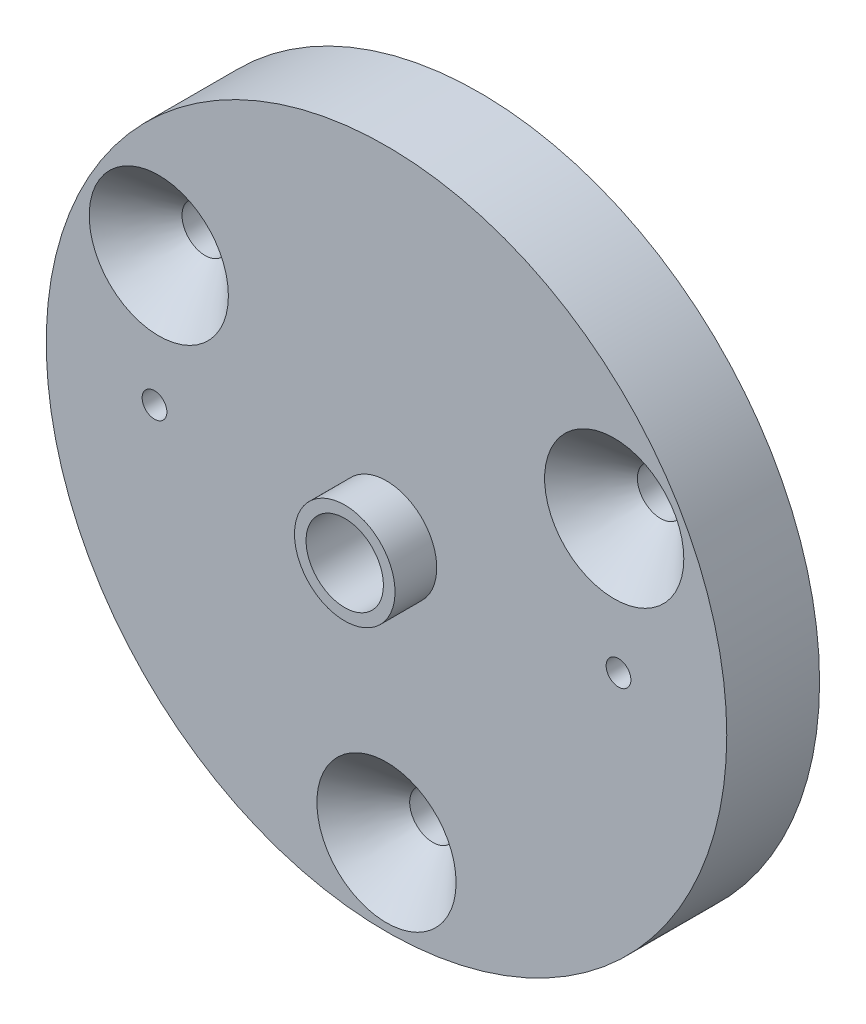
SolidWorks part; units mm, degrees
ref_plane "Спереди" through (0, 0, 0) normal (0, 0, 1) x (1, 0, 0)
ref_plane "Сверху" through (0, 0, 0) normal (0, 1, 0) x (1, 0, 0)
ref_plane "Справа" through (0, 0, 0) normal (1, 0, 0) x (0, 0, -1)
sketch "Эскиз1" plane through (0, 0, 0) normal (0, 0, 1) x (1, 0, 0)
  circle A0 centre (0, 0) radius 22
  dimension "D1" = 44
extrude "Бобышка-Вытянуть1" add sketch "Эскиз1" along normal blind 6
sketch "Эскиз2" plane through (0, 0, 6) normal (0, 0, 1) x (1, 0, 0)
  circle A0 centre (0, 0) radius 3.25
  dimension "D1" = 6.5
extrude "Бобышка-Вытянуть2" add sketch "Эскиз2" along normal blind 2.7
sketch "Эскиз3" plane through (0, 0, 8.7) normal (0, 0, 1) x (1, 0, 0)
  circle A0 centre (0, 0) radius 2.5
  dimension "D1" = 5
extrude "Вырез-Вытянуть1" cut sketch "Эскиз3" against normal through all
sketch "Эскиз4" plane through (0, 0, 6) normal (0, 0, 1) x (1, 0, 0)
  line L0 (-15, 0) -> (15, 0) construction
  circle A0 centre (-15, 0) radius 0.8
  circle A1 centre (15, 0) radius 0.8
  dimension "D1" = 1.6
  dimension "D2" = 15
  dimension "D3" = 30
  dimension "D4" = 15
extrude "Вырез-Вытянуть2" cut sketch "Эскиз4" against normal through all
sketch "Эскиз5" plane through (0, 0, 0) normal (0, 0, -1) x (-1, 0, 0)
  circle A0 centre (0, 0) radius 13
  dimension "D1" = 26
extrude "Вырез-Вытянуть3" cut sketch "Эскиз5" against normal blind 2
sketch "Эскиз6" plane through (0, 0, 6) normal (0, 0, 1) x (1, 0, 0)
  circle A0 centre (0, -17) radius 1.5
  circle A1 centre (-14.7224, 8.5) radius 1.5
  circle A2 centre (14.7224, 8.5) radius 1.5
  point P9 (0, 0)
  dimension "D1" = 3
  dimension "D2" = 0
  dimension "D3" = 17
  dimension "D4" = 3
extrude "Вырез-Вытянуть4" cut sketch "Эскиз6" against normal through all
chamfer "Фаска1" distance 3 angle 45 3 edges at (1.5, -17, 6) (16.2224, 8.5, 6) (-13.2224, 8.5, 6)
